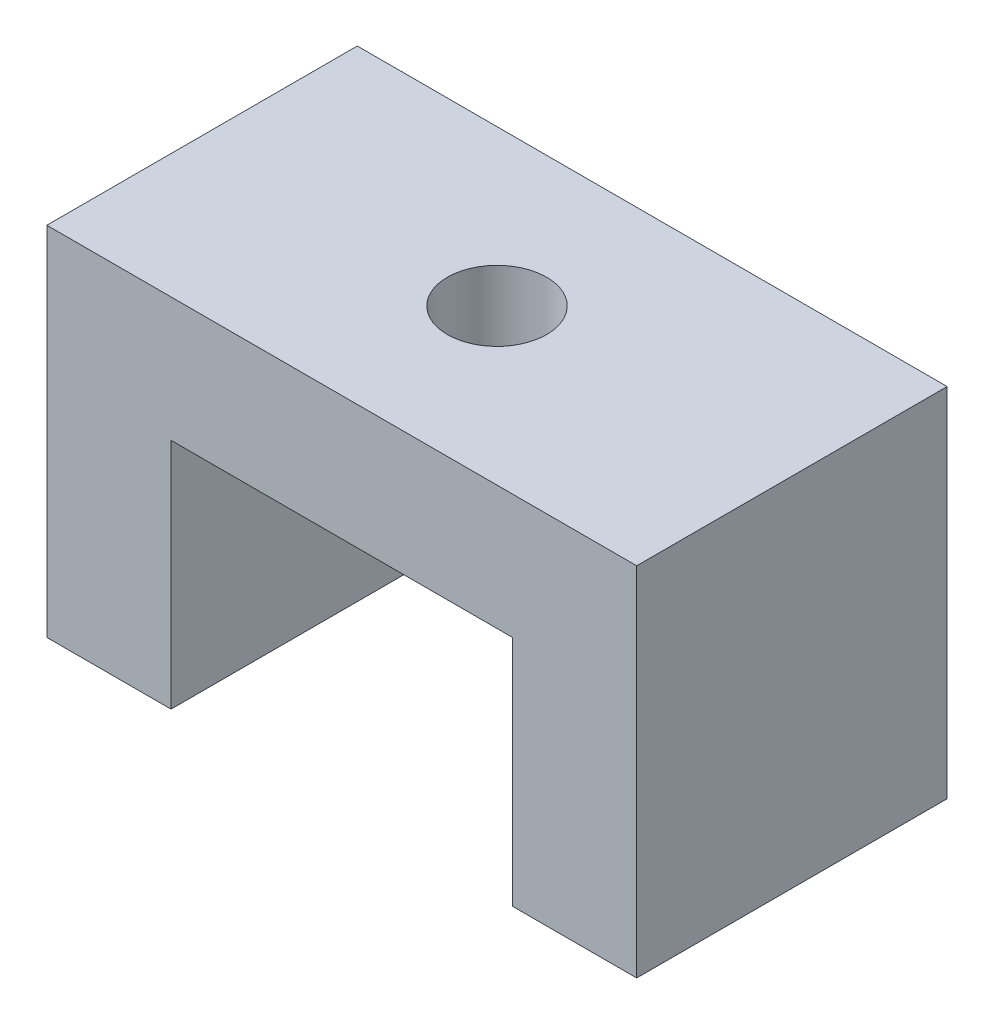
SolidWorks part; units mm, degrees
ref_plane "Plan de face" through (0, 0, 0) normal (0, 0, 1) x (1, 0, 0)
ref_plane "Plan de dessus" through (0, 0, 0) normal (0, 1, 0) x (1, 0, 0)
ref_plane "Plan de droite" through (0, 0, 0) normal (1, 0, 0) x (0, 0, -1)
sketch "Esquisse1" plane through (0, 0, 0) normal (0, 1, 0) x (1, 0, 0)
  line L0 (-19, 10) -> (-19, -10)
  line L1 (0, 0) -> (11, 0) construction
  line L2 (0, 0) -> (-11, 0) construction
  line L3 (0, 0) -> (11, 0) construction
  line L4 (-11, 0) -> (-11, 10)
  line L5 (-11, 10) -> (-19, 10)
  line L7 (-19, -10) -> (-11, -10)
  line L8 (-11, -10) -> (-11, 0)
  line L9 (11, 0) -> (11, 10)
  line L10 (11, 10) -> (19, 10)
  line L12 (19, -10) -> (11, -10)
  line L13 (11, -10) -> (11, 0)
  line L14 (19, -10) -> (19, 10)
  circle A0 centre (-15, 0) radius 2
  circle A1 centre (15, 0) radius 2
extrude "Boss.-Extru.1" add sketch "Esquisse1" along normal blind 15 contours A0 | A1 | L13 L12 L14 L10 L9 A1 | L7 L8 L4 L5 L0 A0 region at (-15, 0, -9.7846) region at (11.2154, 0, -5) region at (-15, 0, 0) region at (15, 0, 0)
sketch "Esquisse3" plane through (0, 15, 0) normal (0, 1, 0) x (1, 0, 0)
  line L0 (-19, -10) -> (19, -10)
  line L1 (19, -10) -> (19, 10)
  line L2 (19, 10) -> (19, -10) construction
  line L3 (19, 10) -> (-19, 10)
  line L4 (-19, 10) -> (-19, -10)
extrude "Boss.-Extru.2" add sketch "Esquisse3" along normal blind 8
sketch "Esquisse4" plane through (0, 23, 0) normal (0, 1, 0) x (1, 0, 0)
  circle A0 centre (0, 0) radius 3.2
extrude "Enlèv. mat.-Extru.1" cut sketch "Esquisse4" against normal blind 10
extrude "Enlèv. mat.-Extru.3" cut sketch "Esquisse1<3>" along normal blind 15 contours A0 | A1 region at (-15, 0, 0) region at (15, 0, 0)
sketch "Esquisse1<3>" plane through (0, 0, 0) normal (0, 1, 0) x (1, 0, 0) same geometry as "Esquisse1"
